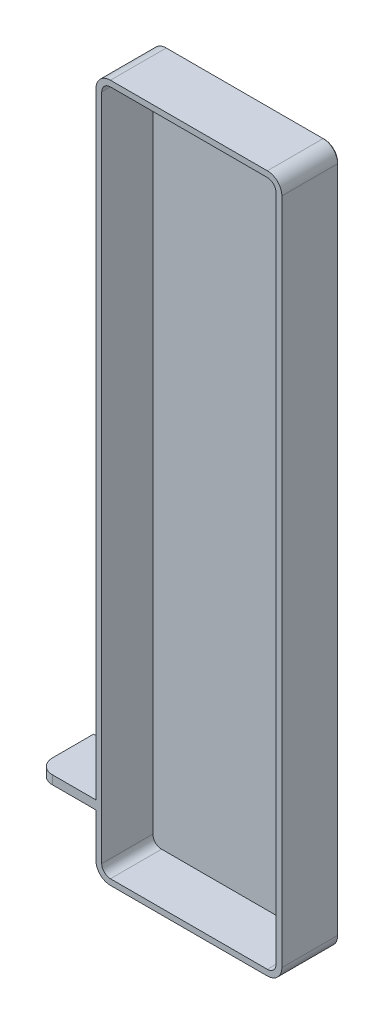
SolidWorks part; units mm, degrees
material "ABS (Black)"
ref_plane "Front Plane" through (0, 0, 0) normal (0, 0, 1) x (1, 0, 0)
ref_plane "Top Plane" through (0, 0, 0) normal (0, 1, 0) x (1, 0, 0)
ref_plane "Right Plane" through (0, 0, 0) normal (1, 0, 0) x (0, 0, -1)
sketch "Sketch1" plane through (0, 0, 0) normal (0, 0, 1) x (1, 0, 0)
  line L1 (-86.7699, 240.5654) -> (-150.7699, 240.5654)
  line L2 (-86.7699, 240.5654) -> (-86.7699, 0.5654)
  line L3 (-86.7699, 0.5654) -> (-150.7699, 0.5654)
  line L4 (-150.7699, 240.5654) -> (-150.7699, 0.5654)
  dimension "D1" = 64
  dimension "D2" = 240
extrude "Boss-Extrude1" add sketch "Sketch1" along normal blind 19.6 separate body
fillet "Fillet1" radius 5 4 edges at (-150.7699, 0.5654, 9.8) (-86.7699, 0.5654, 9.8) (-86.7699, 240.5654, 9.8) (-150.7699, 240.5654, 9.8)
sketch "Sketch3" plane through (0, 0, 19.6) normal (0, 0, 1) x (1, 0, 0)
  line L9 (-148.7699, 235.5654) -> (-148.7699, 5.5654)
  line L10 (-145.7699, 2.5654) -> (-91.7699, 2.5654)
  line L11 (-88.7699, 5.5654) -> (-88.7699, 235.5654)
  line L12 (-91.7699, 238.5654) -> (-145.7699, 238.5654)
  line L13 (-148.7699, 235.5654) -> (-148.7699, 5.5654)
  line L14 (-145.7699, 2.5654) -> (-91.7699, 2.5654)
  line L15 (-88.7699, 5.5654) -> (-88.7699, 235.5654)
  line L16 (-91.7699, 238.5654) -> (-145.7699, 238.5654)
  arc A8 (-148.7699, 5.5654) -> (-145.7699, 2.5654) centre (-145.7699, 5.5654) ccw
  arc A9 (-91.7699, 2.5654) -> (-88.7699, 5.5654) centre (-91.7699, 5.5654) ccw
  arc A10 (-88.7699, 235.5654) -> (-91.7699, 238.5654) centre (-91.7699, 235.5654) ccw
  arc A11 (-145.7699, 238.5654) -> (-148.7699, 235.5654) centre (-145.7699, 235.5654) ccw
  arc A12 (-148.7699, 5.5654) -> (-145.7699, 2.5654) centre (-145.7699, 5.5654) ccw
  arc A13 (-91.7699, 2.5654) -> (-88.7699, 5.5654) centre (-91.7699, 5.5654) ccw
  arc A14 (-88.7699, 235.5654) -> (-91.7699, 238.5654) centre (-91.7699, 235.5654) ccw
  arc A15 (-145.7699, 238.5654) -> (-148.7699, 235.5654) centre (-145.7699, 235.5654) ccw
  dimension "D1" = 2
extrude "Cut-Extrude1" cut sketch "Sketch3" against normal offset from surface (17.6 mm away) 2 up to face at (-118.7699, 120.5654, 0)
sketch "Sketch4" plane through (-150.7699, 0, 0) normal (-1, 0, 0) x (0, 0, 1)
  line L0 (0, 235.5654) -> (0, 5.5654) construction
  line L1 (0, 23.5654) -> (19.6, 23.5654)
  line L2 (0, 23.5654) -> (0, 20.5654)
  line L3 (0, 20.5654) -> (19.6, 20.5654)
  line L4 (19.6, 23.5654) -> (19.6, 20.5654)
  line L5 (19.6, 235.5654) -> (19.6, 5.5654) construction
  line L6 (19.6, 0.5654) -> (0, 0.5654) construction
  dimension "D1" = 3
  dimension "D2" = 20
extrude "Boss-Extrude2" add sketch "Sketch4" along normal blind 20
fillet "Fillet2" radius 5 1 edges at (-170.7699, 22.0654, 19.6)
move or copy body "Body-Move/Copy1" bodies to move or copy 104 copy no translate (0, -0.5654, 0) parameters "D1"=0, "D2"=0.5654, "D3"=0
move or copy body "Body-Move/Copy2" bodies to move or copy 105 copy no translate (150.7699, 0, 0) parameters "D1"=150.7699, "D2"=0, "D3"=0
chamfer "Chamfer1" distance 0.4 12 edges at (62.5355, 1.4645, 0) (64, 120, 0) (62.5355, 238.5355, 0) (32, 240, 0) (1.4645, 238.5355, 0) (0, 129, 0) (-10, 23, 0) (-20, 21.5, 0) (-10, 20, 0) (0, 12.5, 0) (1.4645, 1.4645, 0) (32, 0, 0)
